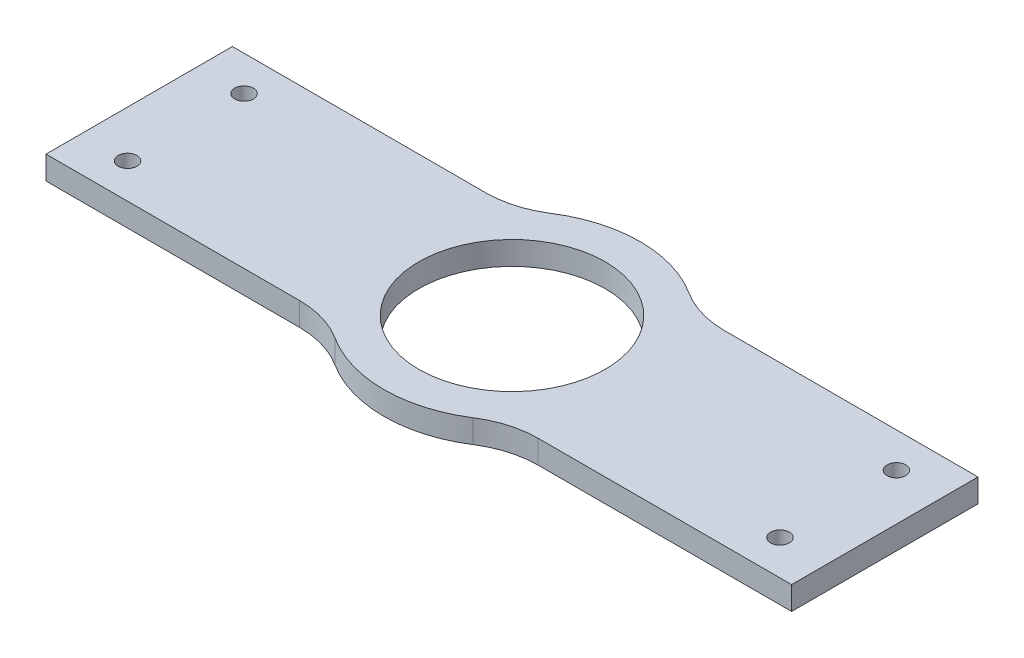
SolidWorks part; units mm, degrees
material "6061-T6 (SS)"
ref_plane "Front" through (0, 0, 0) normal (0, 0, 1) x (1, 0, 0)
ref_plane "Top" through (0, 0, 0) normal (0, 1, 0) x (1, 0, 0)
ref_plane "Right" through (0, 0, 0) normal (1, 0, 0) x (0, 0, -1)
sketch "Sketch1" plane through (0, 0, 0) normal (0, 1, 0) x (1, 0, 0)
  line L0 (203.2, 0) -> (203.2, 19.05) construction
  line L1 (0, 0) -> (69.0659, 0)
  line L2 (0, 0) -> (0, 50.8)
  line L3 (0, 50.8) -> (69.0659, 50.8)
  line L4 (203.2, 0) -> (203.2, 50.8)
  line L5 (0, 50.8) -> (203.2, 0) construction
  line L6 (134.1341, 50.8) -> (203.2, 50.8)
  line L7 (134.1341, 0) -> (203.2, 0)
  arc A0 (82.7645, -4.0105) -> (120.4355, -4.0105) centre (101.6, 25.4) ccw
  arc A1 (120.4355, 54.8105) -> (82.7645, 54.8105) centre (101.6, 25.4) ccw
  arc A2 (69.0659, 0) -> (82.7645, -4.0105) centre (69.0659, -25.4) cw
  arc A3 (134.1341, 0) -> (120.4355, -4.0105) centre (134.1341, -25.4) ccw
  arc A4 (134.1341, 50.8) -> (120.4355, 54.8105) centre (134.1341, 76.2) cw
  arc A5 (69.0659, 50.8) -> (82.7645, 54.8105) centre (69.0659, 76.2) ccw
  point P18 (125.5707, 50.8)
  dimension "D2" = 69.85
  dimension "D3" = 25.4
  dimension "D1" = 50.8
extrude "Boss-Extrude1" add sketch "Sketch1" along normal blind 6.35
sketch "Sketch4" plane through (0, 6.35, 0) normal (0, 1, 0) x (1, 0, 0)
  line L0 (0, 0) -> (12.7, 9.525) construction
  line L1 (0, 0) -> (69.0659, 0) construction
  line L6 (12.7, 9.525) -> (12.7, 41.275) construction
  line L7 (12.7, 41.275) -> (25.4, 50.8) construction
  line L8 (69.0659, 50.8) -> (0, 50.8) construction
  line L9 (101.6, 0) -> (101.6, 25.4) construction
  arc A0 (82.7645, -4.0105) -> (120.4355, -4.0105) centre (101.6, 25.4) ccw construction
  point P0 (12.7, 41.275)
  point P4 (12.7, 9.525)
  point P34 (190.5, 9.525)
  point P36 (190.5, 41.275)
  dimension "D1" = 31.75
  dimension "D2" = 25.4
hole_wizard "#10 Clearance Hole1" positions "Sketch4" profile "Sketch3" hole size "#10" standard "ANSI Inch" end condition up to next
sketch "Sketch3" plane through (12.7, 6.35, -41.275) normal (1, 0, 0) x (0, 0, 1)
  line L0 (0, 0) -> (0, 6.35)
  line L1 (0, 6.35) -> (2.5527, 6.35)
  line L2 (2.5527, 6.35) -> (2.5527, 0)
  line L5 (2.5527, 0) -> (0, 0)
  line L11 (0, -6.35) -> (0, 107.95) construction
  dimension "Thru Hole Dia." = 5.1054
  dimension "Thru Hole Depth" = 6.35
sketch "Sketch5" plane through (0, 6.35, 0) normal (0, 1, 0) x (1, 0, 0)
  circle A0 centre (101.6, 25.4) radius 25.4
  arc A1 (120.4355, 54.8105) -> (82.7645, 54.8105) centre (101.6, 25.4) ccw construction
  dimension "D1" = 50.8
extrude "Cut-Extrude1" cut sketch "Sketch5" against normal through all
